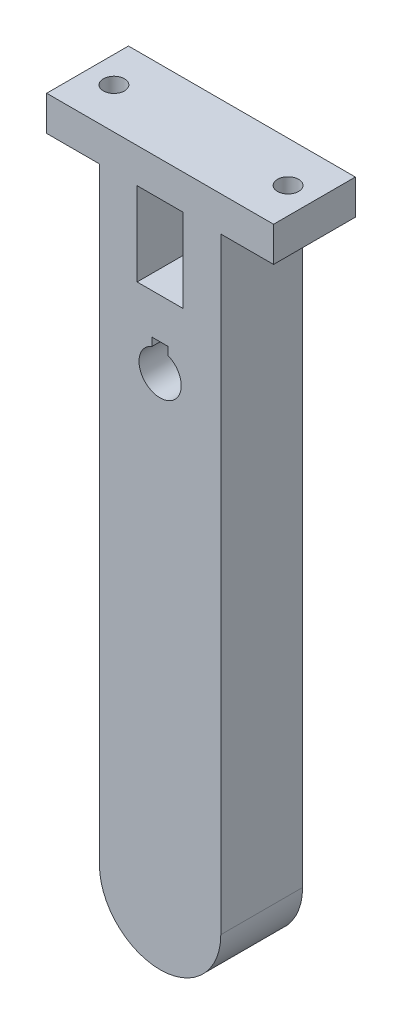
SolidWorks part; units mm, degrees
material "PE a densità alta"
ref_plane "Piano frontale" through (0, 0, 0) normal (0, 0, 1) x (1, 0, 0)
ref_plane "Piano superiore" through (0, 0, 0) normal (0, 1, 0) x (1, 0, 0)
ref_plane "Piano destro" through (0, 0, 0) normal (1, 0, 0) x (0, 0, -1)
sketch "Schizzo3" plane through (0, 0, 0) normal (0, 0, 1) x (1, 0, 0)
  line L0 (-62.6021, -3.8591) -> (-62.6021, 111.1409)
  line L1 (-62.6021, 111.1409) -> (-72.6021, 111.1409)
  line L2 (-72.6021, 111.1409) -> (-72.6021, 117.7409)
  line L3 (-72.6021, 117.7409) -> (-29.6021, 117.7409)
  line L4 (-29.6021, 117.7409) -> (-29.6021, 111.1409)
  line L5 (-29.6021, 111.1409) -> (-39.6021, 111.1409)
  line L6 (-39.6021, 111.1409) -> (-39.6021, -3.8591)
  arc A0 (-62.6021, -3.8591) -> (-39.6021, -3.8591) centre (-51.1021, -3.8591) ccw
  dimension "D1" = 43
  dimension "D2" = 23
sketch "Schizzo6" plane through (0, 0, 0) normal (0, 0, 1) x (1, 0, 0)
  line L9 (-49.6021, 86.199) -> (-49.6021, 87.699)
  line L10 (-52.6021, 86.199) -> (-52.6021, 87.699)
  line L11 (-62.6021, 111.1409) -> (-39.6021, 111.1409)
  line L12 (-52.6021, 87.699) -> (-49.6021, 87.699)
  arc A1 (-52.6021, 86.199) -> (-49.6021, 86.199) centre (-51.1021, 82.4909) ccw
  point P0 (-51.1021, 111.1409)
  dimension "D1" = 28.65
sketch "Schizzo7" plane through (0, 0, 0) normal (0, 0, 1) x (1, 0, 0)
  line L0 (-39.6021, 111.1409) -> (-39.6021, -3.8591) construction
  line L1 (-55.4521, 111.1409) -> (-46.7521, 111.1409)
  line L2 (-55.4521, 111.1409) -> (-55.4521, 95.3409)
  line L3 (-55.4521, 95.3409) -> (-46.7521, 95.3409)
  line L4 (-46.7521, 111.1409) -> (-46.7521, 95.3409)
  line L5 (-62.6021, 111.1409) -> (-39.6021, 111.1409) construction
  line L6 (-62.6021, -3.8591) -> (-62.6021, 111.1409) construction
  point P9 (-51.1021, 95.3409)
  dimension "D1" = 7.15
  dimension "D2" = 7.15
  dimension "D3" = 12.85
  dimension "D4" = 0
extrude "Estrusione-Estrusione1" add sketch "Schizzo3" along normal blind 15.5 contours L3 L4 L5 L6 A0 L0 L1 L2
sketch "Schizzo9" plane through (0, 111.1409, 0) normal (0, -1, 0) x (1, 0, 0)
  circle A0 centre (-34.6021, 7.75) radius 2
  circle A1 centre (-67.6021, 7.75) radius 2
extrude "Taglio-Estrusione4" cut sketch "Schizzo7" along normal blind 15.5 contours L3 L4 L1 L2
extrude "Taglio-Estrusione5" cut sketch "Schizzo6" along normal blind 15.5 contours A1 L9 L12 L10
extrude "Taglio-Estrusione7" cut sketch "Schizzo9" against normal blind 6.6 contours A1
sketch "Schizzo11" plane through (0, 111.1409, 0) normal (0, -1, 0) x (-1, 0, 0)
  circle A0 centre (34.6021, -7.75) radius 2
extrude "Taglio-Estrusione8" cut sketch "Schizzo11" against normal blind 6.6 contours A0
